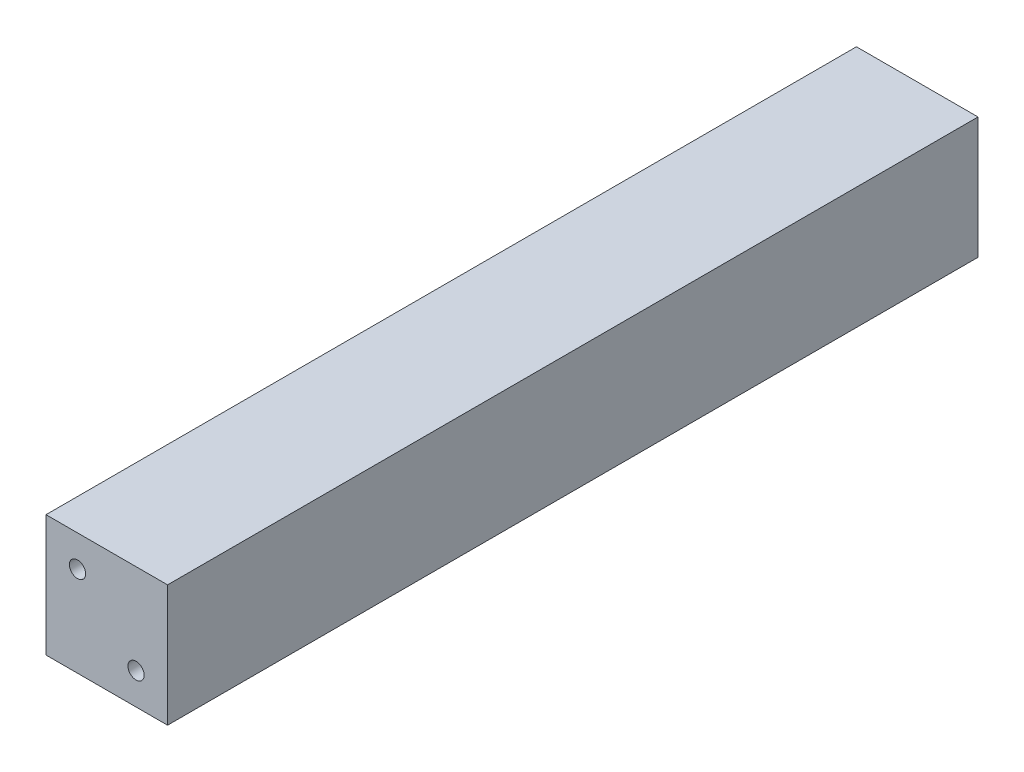
SolidWorks part; units mm, degrees
ref_plane "Alzado" through (0, 0, 0) normal (0, 0, 1) x (1, 0, 0)
ref_plane "Planta" through (0, 0, 0) normal (0, 1, 0) x (1, 0, 0)
ref_plane "Vista lateral" through (0, 0, 0) normal (1, 0, 0) x (0, 0, -1)
sketch "Croquis1" plane through (0, 0, 0) normal (0, 0, 1) x (1, 0, 0)
  line L1 (-15, -15) -> (15, -15)
  line L2 (-15, -15) -> (-15, 15)
  line L3 (-15, 15) -> (15, 15)
  line L4 (15, -15) -> (15, 15)
  line L5 (-15, -15) -> (15, 15) construction
  line L6 (-15, 15) -> (15, -15) construction
  point P0 (0, 0)
  dimension "D1" = 30
extrude "Saliente-Extruir1" add sketch "Croquis1" along normal blind 200
sketch "Croquis2" plane through (0, 0, 200) normal (0, 0, 1) x (1, 0, 0)
  line L0 (-15, 15) -> (15, -15) construction
  line L1 (-15, -15) -> (15, 15) construction
  circle A1 centre (-7.2218, 7.2218) radius 2
  circle A2 centre (7.2218, -7.2218) radius 2
  dimension "D1" = 11
extrude "Cortar-Extruir1" cut sketch "Croquis2" against normal blind 25
sketch "Croquis4" plane through (0, 0, 0) normal (0, 0, -1) x (-1, 0, 0)
  circle A0 centre (0, 0) radius 2
extrude "Cortar-Extruir3" cut sketch "Croquis4" against normal blind 25
